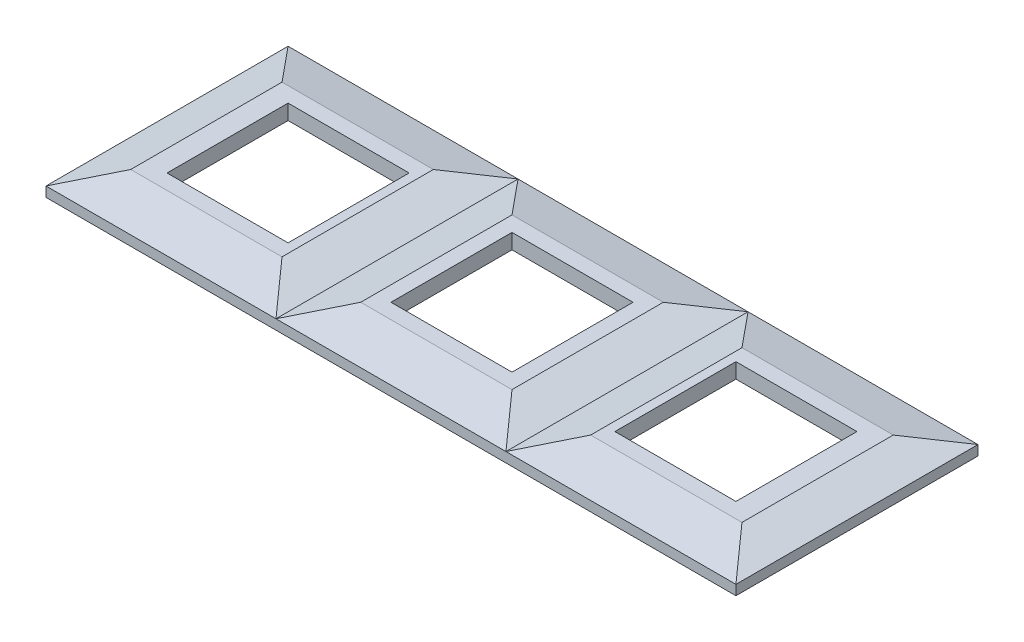
SolidWorks part; units mm, degrees
ref_plane "Спереди" through (0, 0, 0) normal (0, 0, 1) x (1, 0, 0)
ref_plane "Сверху" through (0, 0, 0) normal (0, 1, 0) x (1, 0, 0)
ref_plane "Справа" through (0, 0, 0) normal (1, 0, 0) x (0, 0, -1)
sketch "Эскиз1" plane through (0, 0, 0) normal (0, 0, 1) x (1, 0, 0)
  line L0 (-38, 0) -> (-114, 0)
  line L1 (-114, 0) -> (-114, 3.2778)
  line L2 (-114, 3.2778) -> (-101, 7)
  line L3 (-101, 7) -> (-51, 7)
  line L4 (-76, 36.9052) -> (-76, -25.4966) construction
  line L6 (0, 40.9923) -> (0, -28.3407) construction
  line L7 (38, 0) -> (-38, 0)
  line L9 (-38, 3.2778) -> (-25, 7)
  line L11 (-38, 3.2778) -> (-51, 7)
  line L13 (-25, 7) -> (25, 7)
  line L15 (38, 3.2778) -> (51, 7)
  line L16 (38, 3.2778) -> (25, 7)
  line L18 (101, 7) -> (51, 7)
  line L19 (114, 3.2778) -> (101, 7)
  line L20 (114, 0) -> (114, 3.2778)
  line L21 (38, 0) -> (114, 0)
  line L22 (-38, 0) -> (-38, 3.2778) [skipped]
  point P0 (-76, 0)
  point P6 (-76, 7)
  point P7 (-76, 0)
  point P8 (-76, 7)
  point P15 (0, 0)
  point P16 (0, 7)
  point P21 (0, 7)
  point P24 (0, 0)
  point P27 (76, 7)
  point P28 (76, 0)
  point P31 (0, 0)
  dimension "D1" = 2
extrude "Бобышка-Вытянуть1" add sketch "Эскиз1" along normal mid plane 80
sketch "Эскиз2" plane through (0, 0, 0) normal (1, 0, 0) x (0, 0, -1)
  line L4 (40, 0) -> (-40, 0)
  line L6 (0, 24.25) -> (0, -8.715) construction
  line L9 (-40, 0) -> (-40, 3.2778)
  line L10 (-40, 3.2778) -> (-25, 7)
  line L11 (-40, 7) -> (40, 7) construction
  line L12 (-25, 7) -> (25, 7)
  line L13 (40, 3.2778) -> (25, 7)
  line L14 (40, 0) -> (40, 3.2778)
  point P13 (0, 7)
  point P15 (0, 0)
extrude "Вырез-Вытянуть1" cut sketch "Эскиз2" against normal mid plane 246 flip side to cut
sketch "Эскиз3" plane through (0, 0, 0) normal (0, -1, 0) x (1, 0, 0)
  line L0 (54, 20) -> (94, 20)
  line L1 (-20, 20) -> (20, 20)
  line L2 (-20, 20) -> (-20, -20)
  line L3 (-20, -20) -> (20, -20)
  line L4 (20, 20) -> (20, -20)
  line L5 (-20, 20) -> (20, -20) construction
  line L6 (-20, -20) -> (20, 20) construction
  line L7 (54, 20) -> (54, -20)
  line L8 (54, -20) -> (94, -20)
  line L13 (94, 20) -> (94, -20)
  line L14 (54, 20) -> (94, -20) construction
  line L15 (54, -20) -> (94, 20) construction
  line L16 (-94, 20) -> (-54, 20)
  line L17 (-94, 20) -> (-94, -20)
  line L18 (-94, -20) -> (-54, -20)
  line L19 (-54, 20) -> (-54, -20)
  line L20 (-94, 20) -> (-54, -20) construction
  line L21 (-94, -20) -> (-54, 20) construction
  point P0 (0, 0)
  point P5 (74, 0)
  point P14 (-74, 0)
  dimension "D1" = 2
  dimension "D2" = 2
extrude "Вырез-Вытянуть2" cut sketch "Эскиз3" against normal through all
sketch "Эскиз4" plane through (0, 0, 0) normal (0, -1, 0) x (1, 0, 0)
  line L0 (38.5, 35.5) -> (109.5, 35.5)
  line L1 (-35.5, 35.5) -> (35.5, 35.5)
  line L2 (-35.5, 35.5) -> (-35.5, -35.5)
  line L3 (-35.5, -35.5) -> (35.5, -35.5)
  line L4 (35.5, 35.5) -> (35.5, -35.5)
  line L5 (-35.5, 35.5) -> (35.5, -35.5) construction
  line L6 (-35.5, -35.5) -> (35.5, 35.5) construction
  line L7 (38.5, 35.5) -> (38.5, -35.5)
  line L8 (38.5, -35.5) -> (109.5, -35.5)
  line L13 (109.5, 35.5) -> (109.5, -35.5)
  line L14 (38.5, 35.5) -> (109.5, -35.5) construction
  line L15 (38.5, -35.5) -> (109.5, 35.5) construction
  line L16 (-109.5, 35.5) -> (-38.5, 35.5)
  line L17 (-109.5, 35.5) -> (-109.5, -35.5)
  line L18 (-109.5, -35.5) -> (-38.5, -35.5)
  line L19 (-38.5, 35.5) -> (-38.5, -35.5)
  line L20 (-109.5, 35.5) -> (-38.5, -35.5) construction
  line L21 (-109.5, -35.5) -> (-38.5, 35.5) construction
  point P0 (0, 0)
  point P5 (74, 0)
  point P12 (-74, 0)
  dimension "D1" = 2
  dimension "D2" = 2
extrude "Вырез-Вытянуть3" cut sketch "Эскиз4" against normal blind 2
